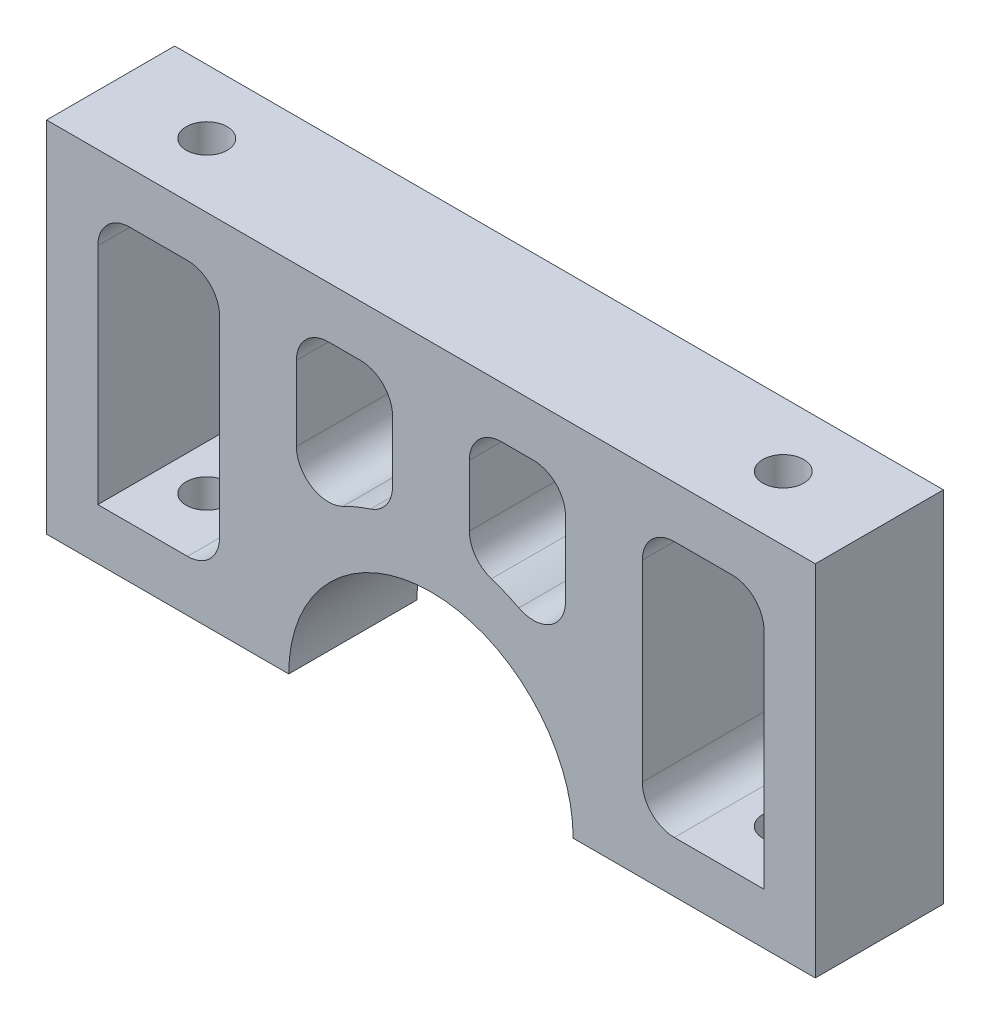
SolidWorks part; units mm, degrees
ref_plane "Front" through (0, 0, 0) normal (0, 0, 1) x (1, 0, 0)
ref_plane "Top" through (0, 0, 0) normal (0, 1, 0) x (1, 0, 0)
ref_plane "Right" through (0, 0, 0) normal (1, 0, 0) x (0, 0, -1)
sketch "ｽｹｯﾁ1" plane through (0, 0, 0) normal (0, 0, 1) x (1, 0, 0)
  line L1 (30, -28) -> (-30, -28)
  line L2 (30, -28) -> (30, 28)
  line L3 (30, 28) -> (-30, 28)
  line L4 (-30, -28) -> (-30, 28)
  line L5 (0, 28) -> (0, -28) construction
  line L6 (30, 0) -> (-30, 0)
  circle A0 centre (0, 0) radius 11.1
  point P0 (0, 0)
  dimension "D3" = 22.2
  dimension "D1" = 60
  dimension "D2" = 56
extrude "ﾎﾞｽ - 押し出し1" add sketch "ｽｹｯﾁ1" along normal blind 10 contours L5 L3 L4 L6 A0 | L3 L5 A0 L6 L2 region at (16.3396, 15.2094, 0) region at (-16.3396, 15.2094, 0)
sketch "ｽｹｯﾁ2" plane through (0, 0, 10) normal (0, 0, 1) x (1, 0, 0)
  line L0 (26, 24) -> (-26, 24)
  line L1 (-26, 24) -> (-26, 4)
  line L2 (-26, 4) -> (-14.5606, 4)
  line L3 (14.5606, 4) -> (26, 4)
  line L4 (26, 4) -> (26, 24)
  line L5 (11.1, 0) -> (30, 0)
  line L6 (30, 0) -> (30, 28)
  line L7 (30, 28) -> (-30, 28)
  line L8 (-30, 28) -> (-30, 0)
  line L9 (-30, 0) -> (-11.1, 0)
  line L10 (11.1, 0) -> (30, 0)
  line L11 (30, 0) -> (30, 28)
  line L12 (30, 28) -> (-30, 28)
  line L13 (-30, 28) -> (-30, 0)
  line L14 (-30, 0) -> (-11.1, 0)
  line L16 (3, 0) -> (-3, 0)
  line L17 (3, 0) -> (3, 24)
  line L18 (3, 24) -> (-3, 24)
  line L19 (-3, 0) -> (-3, 24)
  line L20 (0, 24) -> (0, 0) construction
  line L21 (3, 12) -> (-3, 12) construction
  line L22 (-10.5, 0) -> (-16.5, 0)
  line L23 (-10.5, 0) -> (-10.5, 28)
  line L24 (-10.5, 28) -> (-16.5, 28)
  line L25 (-16.5, 0) -> (-16.5, 28)
  line L26 (-13.5, 28) -> (-13.5, 0) construction
  line L27 (-10.5, 14) -> (-16.5, 14) construction
  line L28 (16.5, 0) -> (10.5, 0)
  line L29 (16.5, 0) -> (16.5, 28)
  line L30 (16.5, 28) -> (10.5, 28)
  line L31 (10.5, 0) -> (10.5, 28)
  line L32 (13.5, 28) -> (13.5, 0) construction
  line L33 (16.5, 14) -> (10.5, 14) construction
  arc A0 (14.5606, 4) -> (-14.5606, 4) centre (0, 0) ccw
  arc A1 (11.1, 0) -> (-11.1, 0) centre (0, 0) ccw
  arc A2 (11.1, 0) -> (-11.1, 0) centre (0, 0) ccw
  point P14 (0, 12)
  point P18 (-13.5, 14)
  point P22 (13.5, 14)
  dimension "D3" = 6
  dimension "D4" = 0
  dimension "D5" = 0
  dimension "D6" = 6
  dimension "D7" = 6
  dimension "D8" = 0
  dimension "D9" = 0
  dimension "7.5" = 7.5
  dimension "D11" = 7.5
  dimension "D1" = 0
  dimension "D2" = 4
extrude "ｶｯﾄ - 押し出し2" cut sketch "ｽｹｯﾁ2" against normal blind 15 contours L29 L3 L4 L0 | A0 L31 L0 L17 | A0 L19 L0 L23 | L2 L25 L0 L1 region at (6.9754, 18.5822, 10) region at (-6.9754, 18.5822, 10) region at (21.25, 14, 10) region at (-21.25, 14, 10)
fillet "ﾌｨﾚｯﾄ1" radius 2.5 14 edges at (-16.5, 4, 5) (-3, 14.799, 5) (10.5, 10.8517, 5) (16.5, 4, 5) (3, 14.799, 5) (-10.5, 10.8517, 5) (16.5, 24, 5) (3, 24, 5) (-10.5, 24, 5) (-26, 24, 5) (26, 24, 5) (10.5, 24, 5) (-3, 24, 5) (-16.5, 24, 5)
sketch "ｽｹｯﾁ3" plane through (0, 28, 0) normal (0, 1, 0) x (1, 0, 0)
  line L0 (30, 0) -> (-30, 0) construction
  line L1 (-30, -10) -> (-30, 0) construction
  line L2 (30, -10) -> (30, 0) construction
  circle A0 centre (-22.5, -5) radius 1.6
  circle A1 centre (22.5, -5) radius 1.6
  dimension "D1" = 3.2
  dimension "D2" = 3.2
  dimension "D3" = 5
  dimension "D4" = 5
  dimension "D5" = 7.5
  dimension "D6" = 7.5
extrude "ｶｯﾄ - 押し出し1" cut sketch "ｽｹｯﾁ3" against normal through all
